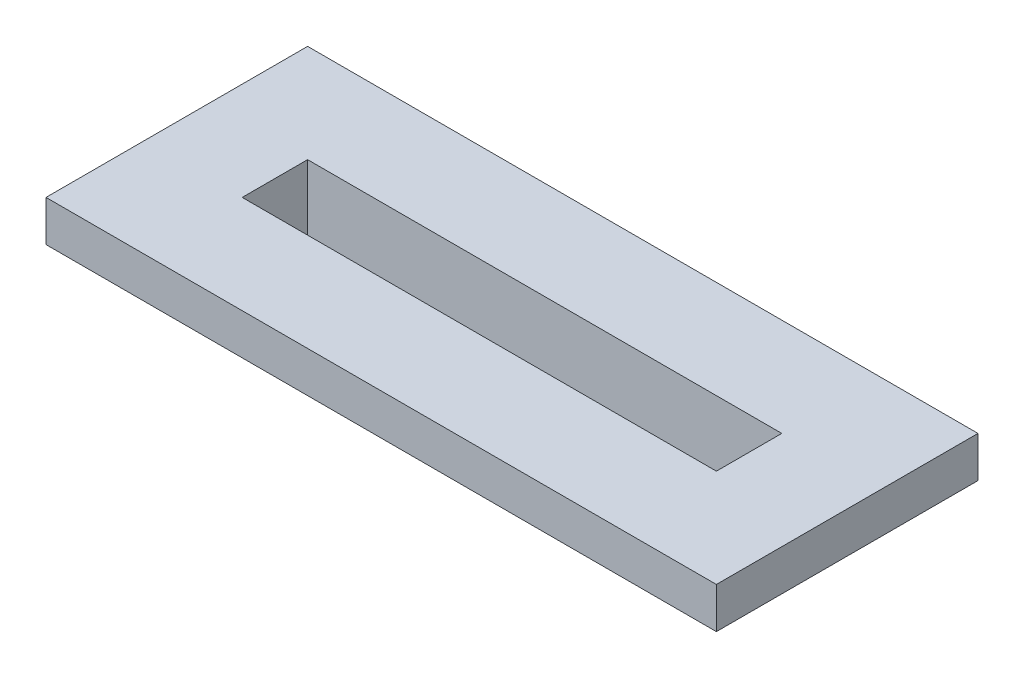
SolidWorks part; units mm, degrees
ref_plane "Front Plane" through (0, 0, 0) normal (0, 0, 1) x (1, 0, 0)
ref_plane "Top Plane" through (0, 0, 0) normal (0, 1, 0) x (1, 0, 0)
ref_plane "Right Plane" through (0, 0, 0) normal (1, 0, 0) x (0, 0, -1)
sketch "Sketch1" plane through (0, 0, 0) normal (0, 1, 0) x (1, 0, 0)
  line L0 (-350, 100) -> (-290, 40) construction
  line L5 (-350, -100) -> (350, -100)
  line L6 (-350, -100) -> (-350, 100)
  line L11 (-350, 100) -> (350, 100)
  line L12 (350, -100) -> (350, 100)
  line L13 (-290, 40) -> (290, 40)
  line L14 (-290, 40) -> (-290, -40)
  line L15 (-290, -40) -> (290, -40)
  line L16 (290, 40) -> (290, -40)
  line L17 (290, 40) -> (350, 100) construction
  line L18 (-290, -40) -> (-350, -100) construction
  line L19 (290, -40) -> (350, -100) construction
  line L20 (0, 40) -> (0, -40) construction
  line L21 (-290, 0) -> (0, 0) construction
  line L22 (0, 0) -> (290, 0) construction
  line L23 (-410, 160) -> (-350, 100) construction
  line L24 (-410, 160) -> (410, 160)
  line L25 (-410, 160) -> (-410, -160)
  line L26 (-410, -160) -> (410, -160)
  line L27 (410, 160) -> (410, -160)
  line L28 (410, 160) -> (350, 100) construction
  line L29 (350, -100) -> (410, -160) construction
  line L30 (-350, -100) -> (-410, -160) construction
  point P18 (0, 0)
  dimension "D1" = 80
  dimension "D2" = 580
  dimension "D3" = 60
  dimension "D4" = 45
  dimension "D5" = 45
  dimension "D6" = 60
extrude "Boss-Extrude1" add sketch "Sketch1" along normal blind 40 and the other way blind 10 contours L27 L24 L25 L26 L12 L5 L6 L11 | L5 L12 L11 L6 L13 L16 L15 L14 region at (-342.7199, 0, 0) region at (0, 0, -151.1977)
extrude "Boss-Extrude2" add sketch "Sketch1<4>" against normal blind 40 contours L5 L12 L11 L6 L13 L16 L15 L14 region at (-342.7199, 0, 0)
sketch "Sketch1<4>" plane through (0, 0, 0) normal (0, 1, 0) x (1, 0, 0) same geometry as "Sketch1"
